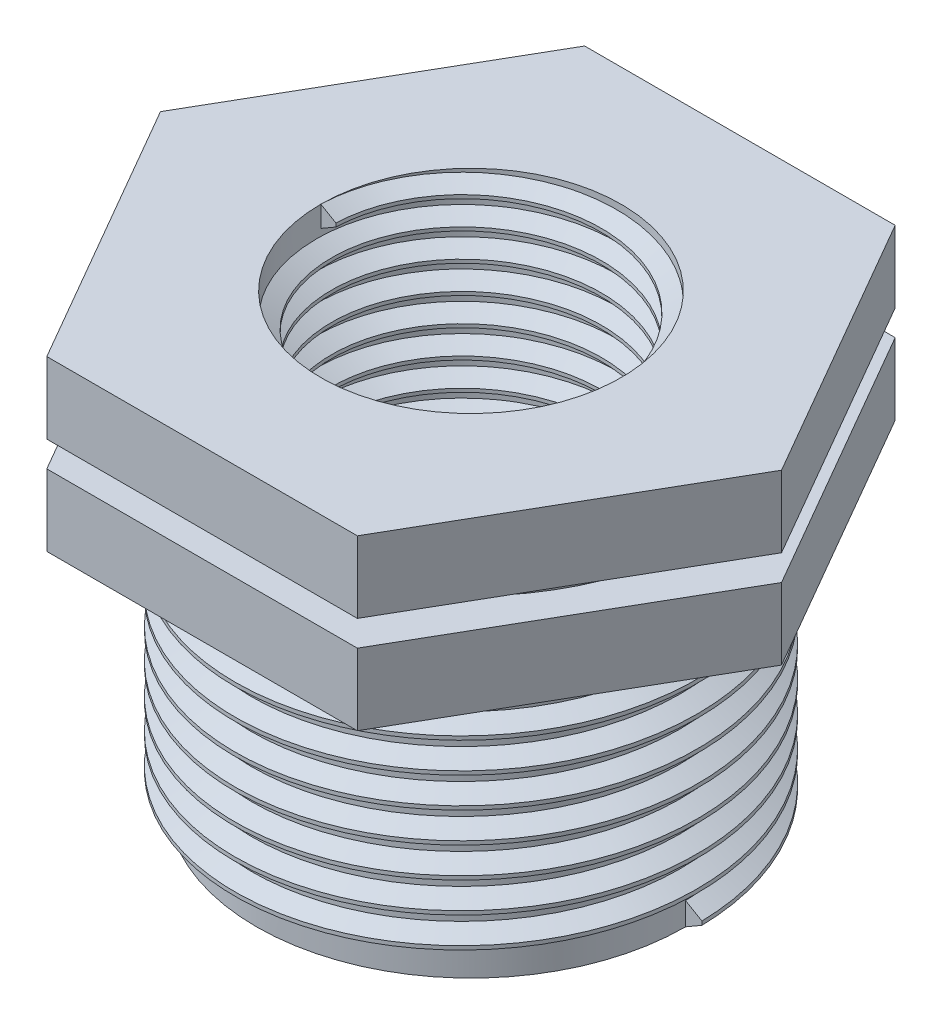
SolidWorks part; units mm, degrees
ref_plane "Płaszczyzna przednia" through (0, 0, 0) normal (0, 0, 1) x (1, 0, 0)
ref_plane "Płaszczyzna górna" through (0, 0, 0) normal (0, 1, 0) x (1, 0, 0)
ref_plane "Płaszczyzna prawa" through (0, 0, 0) normal (1, 0, 0) x (0, 0, -1)
sketch "Szkic1" plane through (0, 0, 0) normal (0, 1, 0) x (1, 0, 0)
  circle A0 centre (0, 0) radius 11.5
  circle A1 centre (0, 0) radius 15
  dimension "D1" = 23
  dimension "D2" = 30
extrude "Dodanie-wyciągnięcie1" add sketch "Szkic1" along normal blind 19.2
sketch "Szkic2" plane through (0, 19.2, 0) normal (0, 1, 0) x (1, 0, 0)
  line L1 (21.7084, 0) -> (10.8542, 18.8)
  line L2 (10.8542, 18.8) -> (-10.8542, 18.8)
  line L3 (-10.8542, 18.8) -> (-21.7084, 0)
  line L4 (-21.7084, 0) -> (-10.8542, -18.8)
  line L5 (-10.8542, -18.8) -> (10.8542, -18.8)
  line L6 (10.8542, -18.8) -> (21.7084, 0)
  circle A0 centre (0, 0) radius 18.8 construction
  circle A1 centre (0, 0) radius 11.5
  dimension "D2" = 23
  dimension "D1" = 37.6
extrude "Dodanie-wyciągnięcie2" add sketch "Szkic2" along normal blind 11.8
sketch "Szkic3" plane through (0, 31, 0) normal (0, 1, 0) x (1, 0, 0)
  circle A0 centre (0, 0) radius 11.5
  circle A1 centre (0, 0) radius 10.5
  dimension "D1" = 21
  dimension "D2" = 23
extrude "Dodanie-wyciągnięcie3" add sketch "Szkic3" against normal blind 17
sketch "Szkic4" plane through (0, 14, 0) normal (0, -1, 0) x (1, 0, 0)
  circle A0 centre (0, 0) radius 11.5
  circle A1 centre (0, 0) radius 8.6
  dimension "D1" = 23
  dimension "D2" = 17.2
extrude "Dodanie-wyciągnięcie5" add sketch "Szkic4" along normal blind 3
sketch "Szkic5" plane through (0, 31, 0) normal (0, 1, 0) x (1, 0, 0)
  line L1 (21.7084, 0) -> (10.8542, 18.8)
  line L2 (10.8542, 18.8) -> (-10.8542, 18.8)
  line L3 (-10.8542, 18.8) -> (-21.7084, 0)
  line L4 (-21.7084, 0) -> (-10.8542, -18.8)
  line L5 (-10.8542, -18.8) -> (10.8542, -18.8)
  line L6 (10.8542, -18.8) -> (21.7084, 0)
  circle A0 centre (0, 0) radius 10.5
  circle A1 centre (0, 0) radius 16.5
  circle A2 centre (0, 0) radius 18.8 construction
  point P4 (0, 0)
  line M1 (10.8542, -18.8) -> (21.7084, 0)
  line M2 (21.7084, 0) -> (10.8542, 18.8)
  line M3 (10.8542, 18.8) -> (-10.8542, 18.8)
  line M4 (-10.8542, 18.8) -> (-21.7084, 0)
  line M5 (-21.7084, 0) -> (-10.8542, -18.8)
  line M6 (-10.8542, -18.8) -> (10.8542, -18.8)
  dimension "D1" = 21
  dimension "D2" = 33
  dimension "D3" = 37.6
extrude "Wytnij-wyciągnięcie1" cut sketch "Szkic5" against normal blind 1.8 from offset 5 contours A1 M6 M1 M2 M3 M4 M5 region at (15.7839, 31, 9.1128) offset against normal yes
thread "Gwint1" pitch 2.1167 method extrude profile "Profil gwintu1" start angle 0, offset 0, length 0, pitch 2.1167, diameter 30
ref_plane "Płaszczyzna1" through (15, 0, 0) normal (0, 0, 1) x (1, 0, 0)
sketch "Profil gwintu1" plane through (15, 0, 0) normal (0, 0, 1) x (1, 0, 0)
  line L0 (0, 0) -> (0, 2.1167) construction
  line L1 (0, 0) -> (1.1457, 0.6615)
  line L2 (1.1457, 0.6615) -> (1.1457, 0.926)
  line L3 (1.1457, 0.926) -> (0, 1.5875)
  line L4 (1.1457, 0.7937) -> (0, 0.7937) construction
  line L11 (0, 0) -> (0, 1.5875)
  point P2 (0, 0)
  dimension "Pitch" = 2.1167
  dimension "Profile_Angle" = 60
  dimension "Profile_Land" = 0.2646
  dimension "Profile_Height" = 1.1457
thread "Gwint2" pitch 1.9538 method extrude profile "Profil gwintu2" start angle 0, offset 0, length 0, pitch 1.9538, diameter 21
ref_plane "Płaszczyzna2" through (-10.5, 31, 0) normal (0, 0, -1) x (1, 0, 0)
sketch "Profil gwintu2" plane through (-10.5, 31, 0) normal (0, 0, -1) x (1, 0, 0)
  line L0 (0, 0) -> (0, 1.9538) construction
  line L1 (0, 0) -> (1.0576, 0.6106)
  line L2 (1.0576, 0.6106) -> (1.0576, 0.8548)
  line L3 (1.0576, 0.8548) -> (0, 1.4654)
  line L4 (1.0576, 0.7327) -> (0, 0.7327) construction
  line L11 (0, 0) -> (0, 1.4654)
  point P2 (0, 0)
  dimension "Pitch" = 1.9538
  dimension "Profile_Angle" = 60
  dimension "Profile_Land" = 0.2442
  dimension "Profile_Height" = 1.0576
